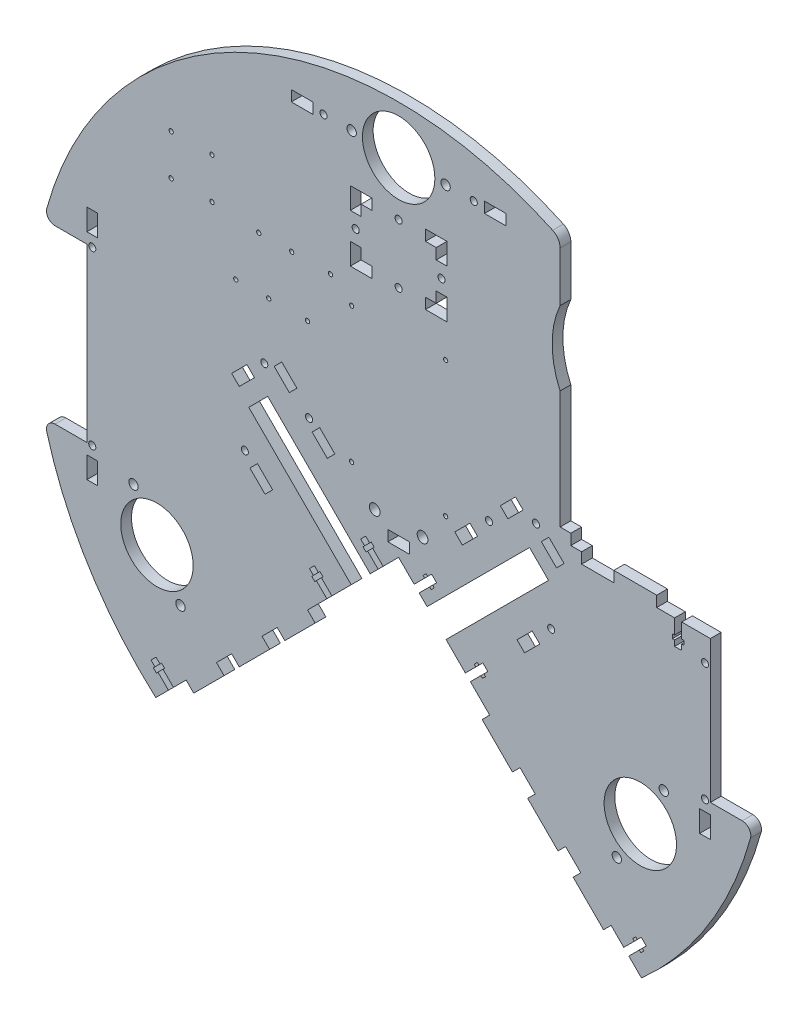
SolidWorks part; units mm, degrees
ref_plane "Front Plane" through (0, 0, 0) normal (0, 0, 1) x (1, 0, 0)
ref_plane "Top Plane" through (0, 0, 0) normal (0, 1, 0) x (1, 0, 0)
ref_plane "Right Plane" through (0, 0, 0) normal (1, 0, 0) x (0, 0, -1)
sketch "Sketch1" plane through (0, 0, 0) normal (0, 0, 1) x (1, 0, 0)
  circle A0 centre (0, 0) radius 215.9
  dimension "D1" = 431.8
extrude "Base Plate Extrusion" add sketch "Sketch1" along normal blind 6.35
sketch "Sketch2" plane through (0, 0, 6.35) normal (0, 0, 1) x (1, 0, 0)
  line L0 (0, 0) -> (0, -230.9791) construction
  line L1 (0, -17.4608) -> (143.6841, -161.1449)
  line L2 (0, -17.4608) -> (-143.6841, -161.1449)
  circle A1 centre (0, 0) radius 215.9 construction
  arc A2 (143.6841, -161.1449) -> (-143.6841, -161.1449) centre (0, 0) cw
  dimension "D1" = 90
  dimension "D2" = 203.2
extrude "V Funnel Cut" cut sketch "Sketch2" against normal through all
sketch "Sketch3" plane through (0, 0, 6.35) normal (0, 0, 1) x (1, 0, 0)
  line L0 (0, 0) -> (251.7982, 0) construction
  line L1 (209.8384, 50.8) -> (184.4384, 50.8)
  line L2 (209.8384, 50.8) -> (209.8384, -50.8)
  line L3 (209.8384, -50.8) -> (184.4384, -50.8)
  line L4 (184.4384, 50.8) -> (184.4384, -50.8)
  arc A0 (143.6841, -161.1449) -> (-143.6841, -161.1449) centre (0, 0) ccw construction
  arc A1 (209.8384, 50.8) -> (209.8384, -50.8) centre (0, 0) cw
  arc M7 (143.6841, -161.1449) -> (-143.6841, -161.1449) centre (0, 0) ccw
  dimension "D1" = 25.4
  dimension "D2" = 101.6
extrude "Wheel Track Cut" cut sketch "Sketch3" against normal through all contours L2 L0 A1 | L4 L0 L2 L1 | L0 L4 L3 L2 | L0 L2 M7 region at (197.1384, 25.4, 6.35) region at (197.1384, -25.4, 6.35) region at (212.266, 19.0862, 6.35) region at (212.266, -19.0862, 6.35)
mirror "Wheel Track Cut Mirror" about plane through (0, 0, 0) normal (1, 0, 0) of "Wheel Track Cut"
sketch "Sketch4" plane through (0, 0, 6.35) normal (0, 0, 1) x (1, 0, 0)
  line L0 (88.68, 15.0926) -> (77.4547, 26.3179)
  line L1 (88.68, 15.0926) -> (28.0633, -45.5241)
  line L2 (77.4547, 26.3179) -> (16.838, -34.2988)
  line L3 (28.0633, -45.5241) -> (16.838, -34.2988)
  line L4 (84.3174, 21.9553) -> (56.956, -5.4061) construction
  line L5 (65.1069, -1.7454) -> (69.5826, 2.7303) construction
  line L6 (65.0924, 7.2204) -> (60.6167, 2.7447) construction
  line L7 (143.6841, -161.1449) -> (0, -17.4608) construction
  dimension "D1" = 15.875
  dimension "D2" = 85.725
extrude "Silo Picker Clearance" cut sketch "Sketch4" against normal through all
sketch "Sketch5" plane through (0, 0, 6.35) normal (0, 0, 1) x (1, 0, 0)
  line L0 (-4.4901, -21.951) -> (0, -17.4608)
  line L1 (-4.4901, -21.951) -> (0, -26.4411)
  line L2 (0, -17.4608) -> (4.4901, -21.951)
  line L3 (0, -26.4411) -> (4.4901, -21.951)
  line L4 (0, -17.4608) -> (-143.6841, -161.1449) construction
  line L6 (4.4901, -21.951) -> (0, -26.4411) construction
  dimension "D1" = 6.35
extrude "V Funnel Corner" add sketch "Sketch5" against normal up to surface (6.35 mm away) up to face at (14.0691, -14.8765, 0)
mirror "Dump Picker Clearance" about plane through (0, 0, 0) normal (1, 0, 0) of "Silo Picker Clearance"
sketch "Sketch6" plane through (8.7304, -8.7304, 0) normal (0.7071, -0.7071, 0) x (0, 0, -1)
  line L0 (-6.35, -52.0342) -> (-6.35, -215.5467) construction
  line L1 (-6.35, -190.1467) -> (0, -190.1467)
  line L2 (-6.35, -190.1467) -> (-6.35, -164.7467)
  line L3 (-6.35, -164.7467) -> (0, -164.7467)
  line L4 (0, -190.1467) -> (0, -164.7467)
  line L5 (0, -52.0342) -> (0, -215.5467) construction
  dimension "D1" = 25.4
  dimension "D2" = 25.4
extrude "V Funnel Tab Left" add sketch "Sketch6" along normal blind 6.35
pattern_linear "V Funnel Tab Pattern Left" count 3 spacing 38.1 along (0.7071, 0.7071, 0) of "V Funnel Tab Left"
sketch "Sketch7" plane through (-8.7304, -8.7304, 0) normal (-0.7071, -0.7071, 0) x (0, 0, 1)
  line L0 (6.35, -215.5467) -> (6.35, -52.0342) construction
  line L1 (6.35, -164.7467) -> (0, -164.7467)
  line L2 (6.35, -164.7467) -> (6.35, -190.1467)
  line L3 (6.35, -190.1467) -> (0, -190.1467)
  line L4 (0, -164.7467) -> (0, -190.1467)
  line L5 (0, -215.5467) -> (0, -52.0342) construction
  dimension "D1" = 25.4
  dimension "D2" = 25.4
extrude "V Funnel Tab Right" add sketch "Sketch7" along normal blind 6.35
pattern_linear "V Funnel Tab Pattern Right" count 3 spacing 38.1 along (-0.7071, 0.7071, 0) of "V Funnel Tab Right"
sketch "Sketch8" plane through (0, 0, 0) normal (0, 0, -1) x (-1, 0, 0)
  line L0 (-70.046, -24.645) -> (-79.0263, -15.6648)
  line L1 (-79.0263, -15.6648) -> (-83.5164, -20.1549)
  line L2 (-83.5164, -20.1549) -> (-74.5361, -29.1352)
  line L3 (-74.5361, -29.1352) -> (-70.046, -24.645)
  line L8 (-97.8965, 28.3267) -> (-88.9163, 37.307)
  line L9 (-88.9163, 37.307) -> (-84.4262, 32.8169)
  line L10 (-84.4262, 32.8169) -> (-93.4064, 23.8366)
  line L11 (-93.4064, 23.8366) -> (-97.8965, 28.3267)
  line L12 (-64.6578, 34.6246) -> (-60.1677, 39.1148)
  line L13 (-60.1677, 39.1148) -> (-69.148, 48.095)
  line L14 (-69.148, 48.095) -> (-73.6381, 43.6049)
  line L15 (-73.6381, 43.6049) -> (-64.6578, 34.6246)
  line L16 (-46.6973, 16.6641) -> (-42.2072, 21.1543)
  line L17 (-42.2072, 21.1543) -> (-33.2269, 12.174)
  line L18 (-33.2269, 12.174) -> (-37.7171, 7.6839)
  line L19 (-37.7171, 7.6839) -> (-46.6973, 16.6641)
  line L21 (-69.148, 48.095) -> (-73.6381, 43.6049) construction
extrude "Silo Arm Tab Holes" cut sketch "Sketch8" against normal blind 6.35
sketch "Sketch10" plane through (0, 0, 0) normal (0, 0, -1) x (-1, 0, 0)
  line L0 (51.1875, 21.1543) -> (42.2072, 12.174)
  line L1 (42.2072, 12.174) -> (37.7171, 16.6641)
  line L2 (37.7171, 16.6641) -> (46.6973, 25.6444)
  line L3 (46.6973, 25.6444) -> (51.1875, 21.1543)
  line L4 (64.6578, 34.6246) -> (60.1677, 39.1148)
  line L5 (60.1677, 39.1148) -> (69.148, 48.095)
  line L6 (69.148, 48.095) -> (73.6381, 43.6049)
  line L7 (73.6381, 43.6049) -> (64.6578, 34.6246)
  line L8 (89.8026, 36.4207) -> (85.3124, 31.9306)
  line L9 (85.3124, 31.9306) -> (94.2927, 22.9503)
  line L10 (94.2927, 22.9503) -> (98.7828, 27.4404)
  line L11 (98.7828, 27.4404) -> (89.8026, 36.4207)
  line L16 (88.0065, -15.6648) -> (83.5164, -11.1747)
  line L17 (83.5164, -11.1747) -> (74.5361, -20.1549)
  line L18 (74.5361, -20.1549) -> (79.0263, -24.645)
  line L19 (79.0263, -24.645) -> (88.0065, -15.6648)
  line L20 (37.7171, 16.6641) -> (42.2072, 12.174) construction
  line L21 (74.5361, -20.1549) -> (79.0263, -24.645) construction
extrude "Dump Arm Tab Holes" cut sketch "Sketch10" against normal blind 6.35
sketch "Sketch11" plane through (0, 0, 0) normal (0, 0, -1) x (-1, 0, 0)
  line L1 (184.4384, -69.85) -> (178.0884, -69.85)
  line L2 (184.4384, -69.85) -> (184.4384, -57.15)
  line L3 (184.4384, -57.15) -> (178.0884, -57.15)
  line L4 (178.0884, -69.85) -> (178.0884, -57.15)
  line L5 (184.4384, 57.15) -> (178.0884, 57.15)
  line L6 (184.4384, 57.15) -> (184.4384, 69.85)
  line L7 (184.4384, 69.85) -> (178.0884, 69.85)
  line L8 (178.0884, 57.15) -> (178.0884, 69.85)
  line L9 (-178.0884, -69.85) -> (-184.4384, -69.85)
  line L10 (-178.0884, -69.85) -> (-178.0884, -57.15)
  line L11 (-178.0884, -57.15) -> (-184.4384, -57.15)
  line L12 (-184.4384, -69.85) -> (-184.4384, -57.15)
  line L13 (-178.0884, 57.15) -> (-184.4384, 57.15)
  line L14 (-178.0884, 57.15) -> (-178.0884, 69.85)
  line L15 (-178.0884, 69.85) -> (-184.4384, 69.85)
  line L16 (-184.4384, 57.15) -> (-184.4384, 69.85)
extrude "Wheel Support Tab Holes" cut sketch "Sketch11" against normal blind 6.35
sketch "Sketch13" plane through (0, 0, 6.35) normal (0, 0, 1) x (1, 0, 0)
  circle A0 centre (0, 187.325) radius 21.4313
  circle A1 centre (27.7812, 187.325) radius 2.7781
  circle A2 centre (-27.7813, 187.325) radius 2.7781
  dimension "D1" = 42.8625
  dimension "D2" = 5.5562
extrude "Caster Wheel Hole" cut sketch "Sketch13" against normal through all
sketch "Sketch14" plane through (0, 0, 6.35) normal (0, 0, 1) x (1, 0, 0)
  line L0 (184.4384, 48.6664) -> (178.0884, 52.9336) construction
  line L1 (184.4384, 50.8) -> (184.4384, -50.8) construction
  line L2 (178.0884, 48.6664) -> (184.4384, 48.6664) construction
  line L3 (184.4384, 52.9336) -> (178.0884, 48.6664) construction
  line L4 (184.4384, -52.9336) -> (178.0884, -48.6664) construction
  line L5 (184.4384, -48.6664) -> (178.0884, -52.9336) construction
  line L6 (178.0884, -48.6664) -> (184.4384, -48.6664) construction
  circle A0 centre (181.2634, 50.8) radius 2.0955
  circle A1 centre (181.2634, -50.8) radius 2.0955
  dimension "D1" = 4.191
extrude "Wheel Support Hole" cut sketch "Sketch14" against normal through all
mirror "Wheel Support Hole Mirror" about plane through (0, 0, 0) normal (1, 0, 0) of "Wheel Support Hole"
sketch "Sketch15" plane through (0, 0, 6.35) normal (0, 0, 1) x (1, 0, 0)
  line L0 (-134.7038, -152.1647) -> (-152.6084, -134.2601) construction
  line L1 (-125.7236, -143.1844) -> (-143.6841, -161.1449) construction
  line L2 (-40.9724, -58.4333) -> (-60.7132, -38.6924) construction
  line L3 (-28.0633, -45.5241) -> (-53.8815, -71.3424) construction
  line L4 (-10.6641, -28.1249) -> (-27.2834, -11.5055) construction
  line L5 (-4.4901, -21.951) -> (-16.838, -34.2988) construction
  line B0 (-136.1856, -153.6464) -> (-133.2221, -150.6829)
  line B1 (-141.2145, -142.6905) -> (-140.2716, -141.7476)
  line B2 (-140.2716, -141.7476) -> (-138.4755, -143.5436)
  line B3 (-138.4755, -143.5436) -> (-139.4185, -144.4866)
  line B4 (-139.4185, -144.4866) -> (-133.2221, -150.6829)
  line B5 (-141.2145, -142.6905) -> (-143.5494, -140.3556)
  line B6 (-143.5494, -140.3556) -> (-146.5129, -143.3191)
  line B7 (-144.178, -145.654) -> (-146.5129, -143.3191)
  line B8 (-142.382, -147.45) -> (-136.1856, -153.6464)
  line B9 (-143.3249, -148.393) -> (-142.382, -147.45)
  line B10 (-145.1209, -146.5969) -> (-143.3249, -148.393)
  line B11 (-144.178, -145.654) -> (-145.1209, -146.5969)
  line B12 (-42.4542, -59.915) -> (-39.4907, -56.9515)
  line B13 (-47.4831, -48.9591) -> (-46.5402, -48.0162)
  line B14 (-46.5402, -48.0162) -> (-44.7441, -49.8122)
  line B15 (-44.7441, -49.8122) -> (-45.6871, -50.7551)
  line B16 (-45.6871, -50.7551) -> (-39.4907, -56.9515)
  line B17 (-47.4831, -48.9591) -> (-49.818, -46.6242)
  line B18 (-49.818, -46.6242) -> (-52.7815, -49.5877)
  line B19 (-50.4466, -51.9226) -> (-52.7815, -49.5877)
  line B20 (-48.6505, -53.7186) -> (-42.4542, -59.915)
  line B21 (-49.5935, -54.6615) -> (-48.6505, -53.7186)
  line B22 (-51.3895, -52.8655) -> (-49.5935, -54.6615)
  line B23 (-50.4466, -51.9226) -> (-51.3895, -52.8655)
  line B24 (-12.1458, -29.6066) -> (-9.1823, -26.6431)
  line B25 (-17.1747, -18.6507) -> (-16.2318, -17.7078)
  line B26 (-16.2318, -17.7078) -> (-14.4358, -19.5038)
  line B27 (-14.4358, -19.5038) -> (-15.3787, -20.4468)
  line B28 (-15.3787, -20.4468) -> (-9.1823, -26.6431)
  line B29 (-17.1747, -18.6507) -> (-19.5096, -16.3159)
  line B30 (-19.5096, -16.3159) -> (-22.4731, -19.2793)
  line B31 (-20.1382, -21.6142) -> (-22.4731, -19.2793)
  line B32 (-18.3422, -23.4103) -> (-12.1458, -29.6066)
  line B33 (-19.2851, -24.3532) -> (-18.3422, -23.4103)
  line B34 (-21.0812, -22.5571) -> (-19.2851, -24.3532)
  line B35 (-20.1382, -21.6142) -> (-21.0812, -22.5571)
sketch_block_instance "TSlot-1"
sketch_block "TSlot" parameters "D1"=3.302, "D2"=2.54, "D3"=3.175, "D4"=8.763, "D5"=1.3462
sketch_block_instance "TSlot-3"
sketch_block_instance "TSlot-4"
extrude "V Funnel T Slot Cut Out" cut sketch "Sketch15" against normal through all
mirror "V Funnel T Slot Cut Out Mirror" about plane through (0, 0, 0) normal (1, 0, 0) of "V Funnel T Slot Cut Out"
sketch "Sketch19" plane through (0, 0, 6.35) normal (0, 0, 1) x (1, 0, 0)
  line L0 (46.5836, 190.5) -> (42.3164, 184.15) construction
  line L1 (46.5836, 184.15) -> (42.3164, 190.5) construction
  line L2 (-42.3164, 190.5) -> (-46.5836, 184.15) construction
  line L3 (-42.3164, 184.15) -> (-46.5836, 190.5) construction
  circle A0 centre (44.45, 187.325) radius 2.0955
  circle A1 centre (-44.45, 187.325) radius 2.0955
  dimension "D1" = 4.191
extrude "Switch Plate Holes" cut sketch "Sketch19" against normal through all
sketch "Sketch20" plane through (0, 0, 0) normal (0, 0, -1) x (-1, 0, 0)
  line L1 (-50.8, 184.15) -> (-63.5, 184.15)
  line L2 (-50.8, 184.15) -> (-50.8, 190.5)
  line L3 (-50.8, 190.5) -> (-63.5, 190.5)
  line L4 (-63.5, 184.15) -> (-63.5, 190.5)
  line L5 (63.5, 184.15) -> (50.8, 184.15)
  line L6 (63.5, 184.15) -> (63.5, 190.5)
  line L7 (63.5, 190.5) -> (50.8, 190.5)
  line L8 (50.8, 184.15) -> (50.8, 190.5)
extrude "Swith Plate Tab Holes" cut sketch "Sketch20" against normal through all
sketch "Sketch26" plane through (0, 0, 6.35) normal (0, 0, 1) x (1, 0, 0)
  line L0 (89.5152, -5.1758) -> (90.988, -12.6833) construction
  line L1 (86.4978, -8.1932) -> (94.0053, -9.666) construction
  line L2 (52.6961, 31.6432) -> (54.1689, 24.1357) construction
  line L3 (49.6788, 28.6258) -> (57.1863, 27.1531) construction
  line L6 (82.0136, 44.2097) -> (80.5408, 36.7022) construction
  line L7 (85.0309, 41.1923) -> (77.5234, 39.7196) construction
  circle A0 centre (90.2516, -8.9296) radius 2.0955
  circle A1 centre (53.4325, 27.8895) radius 2.0955
  circle A3 centre (81.2772, 40.4559) radius 2.0955
  dimension "D1" = 4.191
extrude "Silo Arm Holes" cut sketch "Sketch26" against normal through all
sketch "Sketch27" plane through (0, 0, 6.35) normal (0, 0, 1) x (1, 0, 0)
  line L0 (-49.2298, 28.1768) -> (-56.7373, 26.7041) construction
  line L1 (-52.2471, 31.1942) -> (-53.7199, 23.6867) construction
  line L2 (-80.2116, 46.0116) -> (-78.7389, 38.5041) construction
  line L3 (-83.229, 42.9942) -> (-75.7215, 41.5215) construction
  line L6 (-94.6968, -8.9745) -> (-87.2432, -7.4479) construction
  line L7 (-91.7333, -11.938) -> (-90.2067, -4.4844) construction
  circle A0 centre (-52.9835, 27.4404) radius 2.0955
  circle A1 centre (-79.4753, 42.2579) radius 2.0955
  circle A3 centre (-90.97, -8.2112) radius 2.0955
  dimension "D1" = 4.191
extrude "Dump Arm Holes" cut sketch "Sketch27" against normal through all
fillet "Wheel Slot Fillet" radius 5.08 4 edges at (209.8384, -50.8, 3.175) (209.8384, 50.8, 3.175) (-209.8384, -50.8, 3.175) (-209.8384, 50.8, 3.175)
sketch "Sketch28" plane through (0, 0, 6.35) normal (0, 0, 1) x (1, 0, 0)
  line L0 (0, 0) -> (0, 258.9974) construction
  line L1 (0, 0) -> (249.4479, -144.0188) construction
  line L2 (0, 0) -> (-249.719, -144.1753) construction
  line L3 (-142.9808, -82.55) -> (-156.8714, -58.4907) construction
  line L4 (-27.7813, 187.325) -> (0, 187.325) construction
  line L5 (-142.9808, -82.55) -> (-129.0902, -106.6093) construction
  circle A0 centre (-142.9808, -82.55) radius 21.4313
  circle A1 centre (0, 187.325) radius 21.4313 construction
  circle A2 centre (-156.8714, -58.4907) radius 2.7781
  circle A3 centre (-27.7813, 187.325) radius 2.7781 construction
  circle A4 centre (-129.0902, -106.6093) radius 2.7781
  dimension "D1" = 120
  dimension "D2" = 120
  dimension "D3" = 165.1
extrude "Front Caster Holes" cut sketch "Sketch28" against normal through all
mirror "Front Caster Hole Mirror" about plane through (0, 0, 0) normal (1, 0, 0) of "Front Caster Holes"
sketch "Gyro Holes" plane through (0, 0, 6.35) normal (0, 0, 1) x (1, 0, 0)
  line L1 (-134.5682, 109.4626) -> (-110.4382, 109.4626) construction
  line L2 (-134.5682, 109.4626) -> (-134.5682, 133.5926) construction
  line L3 (-134.5682, 133.5926) -> (-110.4382, 133.5926) construction
  line L4 (-110.4382, 109.4626) -> (-110.4382, 133.5926) construction
  line L5 (-134.5682, 109.4626) -> (-110.4382, 133.5926) construction
  line L6 (-134.5682, 133.5926) -> (-110.4382, 109.4626) construction
  circle A0 centre (-134.5682, 133.5926) radius 1.27
  circle A1 centre (-110.4382, 133.5926) radius 1.27
  circle A2 centre (-110.4382, 109.4626) radius 1.27
  circle A3 centre (-134.5682, 109.4626) radius 1.27
  point P0 (-122.5032, 121.5276)
  dimension "D2" = 24.13
  dimension "D1" = 2.54
extrude "GyroHoles" cut sketch "Gyro Holes" against normal through all
sketch "MotorControllerHoleSketch" plane through (0, 0, 6.35) normal (0, 0, 1) x (1, 0, 0)
  line L0 (0, 215.9) -> (0, -26.4411) construction
  line L2 (-27.82, 17.5746) -> (27.82, 17.5746) construction
  line L3 (-27.82, 17.5746) -> (-27.82, 97.6146) construction
  line L4 (-27.82, 97.6146) -> (27.82, 97.6146) construction
  line L5 (27.82, 17.5746) -> (27.82, 97.6146) construction
  line L6 (-27.82, 17.5746) -> (27.82, 97.6146) construction
  line L7 (-27.82, 97.6146) -> (27.82, 17.5746) construction
  arc A0 (208.1777, 57.2265) -> (-208.1777, 57.2265) centre (0, 0) ccw construction
  circle A1 centre (-27.82, 97.6146) radius 1.25
  circle A2 centre (27.82, 97.6146) radius 1.25
  circle A3 centre (27.82, 17.5746) radius 1.25
  circle A4 centre (-27.82, 17.5746) radius 1.25
  point P6 (0, 57.5946)
  dimension "D1" = 2.5
  dimension "D2" = 55.64
  dimension "D3" = 80.04
extrude "Motor Controller Hole" cut sketch "MotorControllerHoleSketch" against normal through all
sketch "Sketch31" plane through (0, 0, 6.35) normal (0, 0, 1) x (1, 0, 0)
  line L0 (-58.5988, 118.6025) -> (-58.5988, 61.2016) construction
  line L1 (-40.3087, 76.7541) -> (-53.9191, 76.7541) construction
  line L2 (-40.3087, 76.7541) -> (-40.3087, 107.5065) construction
  line L3 (-40.3087, 107.5065) -> (-53.9191, 107.5065) construction
  line L4 (-53.9191, 76.7541) -> (-53.9191, 107.5065) construction
  line L5 (-40.3087, 76.7541) -> (-53.9191, 107.5065) construction
  line L6 (-40.3087, 107.5065) -> (-53.9191, 76.7541) construction
  line L7 (-63.2785, 76.7541) -> (-76.8888, 76.7541) construction
  line L8 (-63.2785, 76.7541) -> (-63.2785, 107.5065) construction
  line L9 (-63.2785, 107.5065) -> (-76.8888, 107.5065) construction
  line L10 (-76.8888, 76.7541) -> (-76.8888, 107.5065) construction
  line L11 (-63.2785, 76.7541) -> (-76.8888, 107.5065) construction
  line L12 (-63.2785, 107.5065) -> (-76.8888, 76.7541) construction
  line L13 (-70.0836, 92.1303) -> (-47.1139, 92.1303) construction
  line L15 (-82.7354, 76.7541) -> (-96.3457, 76.7541) construction
  line L16 (-82.7354, 76.7541) -> (-82.7354, 107.5065) construction
  line L17 (-82.7354, 107.5065) -> (-96.3457, 107.5065) construction
  line L18 (-96.3457, 76.7541) -> (-96.3457, 107.5065) construction
  line L19 (-82.7354, 76.7541) -> (-96.3457, 107.5065) construction
  line L20 (-82.7354, 107.5065) -> (-96.3457, 76.7541) construction
  circle A0 centre (-76.8888, 76.7541) radius 1.27
  circle A1 centre (-63.2785, 107.5065) radius 1.27
  circle A2 centre (-53.9191, 76.7541) radius 1.27
  circle A3 centre (-40.3087, 107.5065) radius 1.27
  circle A4 centre (-82.7354, 107.5065) radius 1.27
  circle A5 centre (-96.3457, 76.7541) radius 1.27
  point P0 (-47.1139, 92.1303)
  point P5 (-70.0836, 92.1303)
  point P18 (-89.5406, 92.1303)
  dimension "D1" = 2.54
  dimension "D2" = 33.6296
extrude "BuckConverterHoles" cut sketch "Sketch31" against normal through all
sketch "Sketch34" plane through (0, 0, 0) normal (0, 0, -1) x (-1, 0, 0)
  line L1 (-28.575, 158.75) -> (-15.875, 158.75)
  line L2 (-28.575, 158.75) -> (-28.575, 152.4)
  line L3 (-22.225, 152.4) -> (-15.875, 152.4)
  line L4 (-15.875, 158.75) -> (-15.875, 152.4)
  line L5 (15.875, 158.75) -> (28.575, 158.75)
  line L6 (15.875, 158.75) -> (15.875, 152.4)
  line L7 (15.875, 152.4) -> (22.225, 152.4)
  line L8 (28.575, 158.75) -> (28.575, 152.4)
  line L9 (15.875, 123.825) -> (22.225, 123.825)
  line L10 (15.875, 123.825) -> (15.875, 117.475)
  line L11 (15.875, 117.475) -> (28.575, 117.475)
  line L12 (28.575, 123.825) -> (28.575, 117.475)
  line L13 (-22.225, 123.825) -> (-15.875, 123.825)
  line L14 (-28.575, 123.825) -> (-28.575, 117.475)
  line L15 (-28.575, 117.475) -> (-15.875, 117.475)
  line L16 (-15.875, 123.825) -> (-15.875, 117.475)
  line L17 (-28.575, 130.175) -> (-22.225, 130.175)
  line L18 (-28.575, 130.175) -> (-28.575, 123.825)
  line L20 (-22.225, 130.175) -> (-22.225, 123.825)
  line L22 (-28.575, 152.4) -> (-28.575, 146.05)
  line L23 (-28.575, 146.05) -> (-22.225, 146.05)
  line L24 (-22.225, 152.4) -> (-22.225, 146.05)
  line L26 (22.225, 152.4) -> (22.225, 146.05)
  line L27 (22.225, 146.05) -> (28.575, 146.05)
  line L28 (28.575, 152.4) -> (28.575, 146.05)
  line L29 (22.225, 130.175) -> (28.575, 130.175)
  line L30 (22.225, 130.175) -> (22.225, 123.825)
  line L32 (28.575, 130.175) -> (28.575, 123.825)
extrude "Cut-Extrude6" cut sketch "Sketch34" against normal through all
sketch "Sketch35" plane through (0, 0, 6.35) normal (0, 0, 1) x (1, 0, 0)
  line L0 (-22.225, 136.017) -> (-28.575, 140.208) construction
  line L1 (-28.575, 136.017) -> (-22.225, 140.208) construction
  line L2 (-2.0955, 152.4) -> (2.0955, 158.75) construction
  line L3 (2.0955, 152.4) -> (-2.0955, 158.75) construction
  line L4 (22.225, 136.017) -> (28.575, 140.208) construction
  line L5 (22.225, 140.208) -> (28.575, 136.017) construction
  line L6 (2.0955, 123.825) -> (-2.0955, 117.475) construction
  line L7 (-2.0955, 123.825) -> (2.0955, 117.475) construction
  circle A0 centre (0, 120.65) radius 2.0955
  circle A1 centre (25.4, 138.1125) radius 2.0955
  circle A2 centre (0, 155.575) radius 2.0955
  circle A3 centre (-25.4, 138.1125) radius 2.0955
  dimension "D1" = 4.191
extrude "Cut-Extrude7" cut sketch "Sketch35" against normal through all
sketch "Sketch37" [suppressed] plane through (0, 0, 0) normal (0, 0, -1) x (-1, 0, 0)
  line L0 (-86.0134, 49.1901) -> (-174.9134, 49.1901) construction
  line L1 (-117.7634, 49.1901) -> (-143.1634, 49.1901)
  line L2 (-117.7634, 49.1901) -> (-117.7634, 55.5401)
  line L3 (-117.7634, 55.5401) -> (-143.1634, 55.5401)
  line L4 (-143.1634, 49.1901) -> (-143.1634, 55.5401)
  line L5 (-117.7634, 49.1901) -> (-117.7634, 55.5401) construction
sketch "Sketch41" plane through (0, 0, 6.35) normal (0, 0, 1) x (1, 0, 0)
  line L0 (95.5384, 193.611) -> (95.5384, 45.8763)
  line L1 (95.5384, 33.1763) -> (95.5384, -193.611) construction
  line L2 (95.5384, 45.8763) -> (101.8884, 45.8763)
  line L3 (101.8884, 45.8763) -> (101.8884, 39.5263)
  line L4 (101.8884, 39.5263) -> (108.2384, 39.5263)
  line L5 (108.2384, 39.5263) -> (108.2384, 33.1763)
  line L6 (108.2384, 33.1763) -> (218.8605, 33.1763)
  line L7 (218.8605, 33.1763) -> (218.8605, 193.611)
  line L8 (218.8605, 193.611) -> (95.5384, 193.611)
  arc A0 (208.1777, 57.2265) -> (-208.1777, 57.2265) centre (0, 0) ccw construction
extrude "Cut-Extrude13" cut sketch "Sketch41" against normal through all
fillet "Fillet1" radius 7.62 1 edges at (95.5384, 193.611, 3.175)
sketch "Sketch42" plane through (0, 0, 6.35) normal (0, 0, 1) x (1, 0, 0)
  line L0 (95.5384, 159.3081) -> (95.5384, 115.5739)
  line L1 (95.5384, 188.8145) -> (95.5384, 45.8763) construction
  arc A1 (95.5384, 115.5739) -> (95.5384, 159.3081) centre (143.7787, 137.441) cw
extrude "Cut-Extrude14" cut sketch "Sketch42" against normal through all
sketch "Sketch44" plane through (0, 33.1763, 0) normal (0, 1, 0) x (1, 0, 0)
  line L0 (108.2384, -6.35) -> (184.4384, -6.35) construction
  line L1 (127.2884, -6.35) -> (152.6884, -6.35)
  line L2 (127.2884, -6.35) -> (127.2884, 0)
  line L3 (127.2884, 0) -> (152.6884, 0)
  line L4 (152.6884, -6.35) -> (152.6884, 0)
  line L5 (108.2384, 0) -> (184.4384, 0) construction
extrude "Boss-Extrude2" add sketch "Sketch44" along normal blind 6.35
sketch "Sketch45" plane through (0, 0, 6.35) normal (0, 0, 1) x (1, 0, 0)
  line L0 (152.6884, 33.1763) -> (184.4384, 33.1763) construction
  line L1 (163.2929, 39.5263) -> (163.2929, 33.1763) construction
  line B0 (167.4839, 33.1763) -> (163.2929, 33.1763)
  line B1 (163.2929, 21.8733) -> (161.9594, 21.8733)
  line B2 (161.9594, 21.8733) -> (161.9594, 24.4133)
  line B3 (161.9594, 24.4133) -> (163.2929, 24.4133)
  line B4 (163.2929, 24.4133) -> (163.2929, 33.1763)
  line B5 (163.2929, 21.8733) -> (163.2929, 18.5713)
  line B6 (163.2929, 18.5713) -> (167.4839, 18.5713)
  line B7 (167.4839, 21.8733) -> (167.4839, 18.5713)
  line B8 (167.4839, 24.4133) -> (167.4839, 33.1763)
  line B9 (168.8174, 24.4133) -> (167.4839, 24.4133)
  line B10 (168.8174, 21.8733) -> (168.8174, 24.4133)
  line B11 (167.4839, 21.8733) -> (168.8174, 21.8733)
  line B12 (165.3884, 33.1763) -> (165.3884, 18.5713) construction
  line B13 (161.9594, 23.1433) -> (172.0532, 23.1433) construction
sketch_block_instance "TSlot-7"
extrude "Cut-Extrude15" cut sketch "Sketch45" against normal through all
sketch "Sketch47" plane through (0, 0, 0) normal (0, 0, -1) x (-1, 0, 0)
  line L1 (-6.35, -12.6983) -> (6.35, -12.6983)
  line L2 (-6.35, -12.6983) -> (-6.35, -6.3483)
  line L3 (-6.35, -6.3483) -> (6.35, -6.3483)
  line L4 (6.35, -12.6983) -> (6.35, -6.3483)
extrude "Cut-Extrude16" cut sketch "Sketch47" against normal through all
extrude "Boss-Extrude1" [suppressed] add sketch "Sketch37" against normal up to surface (6.35 mm away) up to face at (0, -9.5233, 6.35)
sketch "Sketch38" plane through (0, 0, 0) normal (0, 0, -1) x (-1, 0, 0)
  line L2 (-186.392, 104.3946) -> (-275.292, 104.3946) construction
  line L4 (-143.1634, 55.5401) -> (-143.1634, 49.1901) construction
  line L5 (-268.942, 186.9446) -> (-268.942, 110.7446) construction
  line L7 (-192.742, 110.7446) -> (-192.742, 186.9446) construction
  line L8 (-117.7634, 49.1901) -> (-117.7634, 55.5401) construction
  line B0 (-153.1572, 104.3946) -> (-157.3482, 104.3946)
  line B1 (-157.3482, 93.0916) -> (-158.6817, 93.0916)
  line B2 (-158.6817, 93.0916) -> (-158.6817, 95.6316)
  line B3 (-158.6817, 95.6316) -> (-157.3482, 95.6316)
  line B4 (-157.3482, 95.6316) -> (-157.3482, 104.3946)
  line B5 (-157.3482, 93.0916) -> (-157.3482, 89.7896)
  line B6 (-157.3482, 89.7896) -> (-153.1572, 89.7896)
  line B7 (-153.1572, 93.0916) -> (-153.1572, 89.7896)
  line B8 (-153.1572, 95.6316) -> (-153.1572, 104.3946)
  line B9 (-151.8237, 95.6316) -> (-153.1572, 95.6316)
  line B10 (-151.8237, 93.0916) -> (-151.8237, 95.6316)
  line B11 (-153.1572, 93.0916) -> (-151.8237, 93.0916)
  line B12 (-155.2527, 104.3946) -> (-155.2527, 89.7896) construction
  line B13 (-203.9572, 104.3946) -> (-208.1482, 104.3946)
  line B14 (-208.1482, 93.0916) -> (-209.4817, 93.0916)
  line B15 (-209.4817, 93.0916) -> (-209.4817, 95.6316)
  line B16 (-209.4817, 95.6316) -> (-208.1482, 95.6316)
  line B17 (-208.1482, 95.6316) -> (-208.1482, 104.3946)
  line B18 (-208.1482, 93.0916) -> (-208.1482, 89.7896)
  line B19 (-208.1482, 89.7896) -> (-203.9572, 89.7896)
  line B20 (-203.9572, 93.0916) -> (-203.9572, 89.7896)
  line B21 (-203.9572, 95.6316) -> (-203.9572, 104.3946)
  line B22 (-202.6237, 95.6316) -> (-203.9572, 95.6316)
  line B23 (-202.6237, 93.0916) -> (-202.6237, 95.6316)
  line B24 (-203.9572, 93.0916) -> (-202.6237, 93.0916)
  line B25 (-206.0527, 104.3946) -> (-206.0527, 89.7896) construction
sketch_block_instance "TSlot-5"
sketch_block_instance "TSlot-6"
extrude "Cut-Extrude9" [suppressed] cut sketch "Sketch38" against normal through all
sketch "Sketch39" plane through (0, 0, 0) normal (0, 0, -1) x (-1, 0, 0)
  line L0 (-184.4384, 33.1763) -> (-227.6876, 33.1763)
  line L1 (-95.5384, 33.1763) -> (-184.4384, 33.1763)
  line L2 (-95.5384, 33.1763) -> (-95.5384, 122.0763)
  line L3 (-95.5384, 122.0763) -> (-184.4384, 122.0763)
  arc A0 (-227.6876, 33.1763) -> (-184.4384, 122.0763) centre (-22.9914, -11.4365) cw
extrude "Cut-Extrude11" cut sketch "Sketch39" against normal through all
sketch "Sketch40" plane through (0, 0, 6.35) normal (0, 0, 1) x (1, 0, 0)
  line L0 (178.0884, 21.1455) -> (184.4384, 16.9545) construction
  line L1 (184.4384, 33.1763) -> (184.4384, -50.8) construction
  line L2 (178.0884, 16.9545) -> (184.4384, 16.9545) construction
  line L3 (178.0884, 16.9545) -> (184.4384, 21.1455) construction
  circle A0 centre (181.2634, 19.05) radius 2.0955
  dimension "D1" = 4.191
extrude "Cut-Extrude12" cut sketch "Sketch40" against normal through all
sketch "Sketch48" plane through (0, 33.1763, 0) normal (0, 1, 0) x (1, 0, 0)
  line L0 (95.5384, 0) -> (163.2929, 0) construction
  line L1 (95.5384, -6.35) -> (108.2384, -6.35)
  line L2 (95.5384, -6.35) -> (95.5384, 0)
  line L3 (95.5384, 0) -> (108.2384, 0)
  line L4 (108.2384, -6.35) -> (108.2384, 0)
extrude "Boss-Extrude3" add sketch "Sketch48" along normal blind 6.35
sketch "Sketch49" plane through (95.5384, 0, 0) normal (1, 0, 0) x (0, 0, -1)
  line L0 (0, 115.5739) -> (0, 39.5263) construction
  line L1 (-6.35, 39.5263) -> (0, 39.5263)
  line L2 (-6.35, 39.5263) -> (-6.35, 45.8763)
  line L3 (-6.35, 45.8763) -> (0, 45.8763)
  line L4 (0, 39.5263) -> (0, 45.8763)
  line L5 (0, 45.8763) -> (-6.35, 45.8763) construction
extrude "Boss-Extrude4" add sketch "Sketch49" along normal blind 6.35
sketch "Sketch50" plane through (0, 0, 0) normal (0, 0, -1) x (-1, 0, 0)
  line L0 (0, -17.4608) -> (-4.4901, -21.951)
  line L1 (-4.4901, -21.951) -> (0, -26.4411)
  line L2 (0, -26.4411) -> (4.4901, -21.951)
  line L3 (4.4901, -21.951) -> (0, -17.4608)
extrude "Cut-Extrude17" cut sketch "Sketch50" against normal through all
sketch "Sketch51" plane through (0, 0, 0) normal (0, 0, -1) x (-1, 0, 0)
  line L0 (0, 0) -> (0, 11.938) construction
  circle A0 centre (14.1392, 0) radius 3.175
  circle A1 centre (-14.1392, 0) radius 3.175
  dimension "D1" = 6.35
extrude "Cut-Extrude18" cut sketch "Sketch51" against normal through all
sketch "Sketch52" plane through (0, 33.1763, 0) normal (0, 1, 0) x (1, 0, 0)
  line L0 (108.2384, -6.35) -> (163.2929, -6.35) construction
  line L1 (127.2884, -6.35) -> (152.6884, -6.35)
  line L2 (127.2884, -6.35) -> (127.2884, 0)
  line L3 (127.2884, 0) -> (152.6884, 0)
  line L4 (152.6884, -6.35) -> (152.6884, 0)
  line L5 (127.2884, -6.35) -> (127.2884, 0) construction
  line L6 (108.2384, 0) -> (163.2929, 0) construction
  line L7 (152.6884, -6.35) -> (152.6884, 0) construction
extrude "Boss-Extrude5" add sketch "Sketch52" along normal blind 6.35
